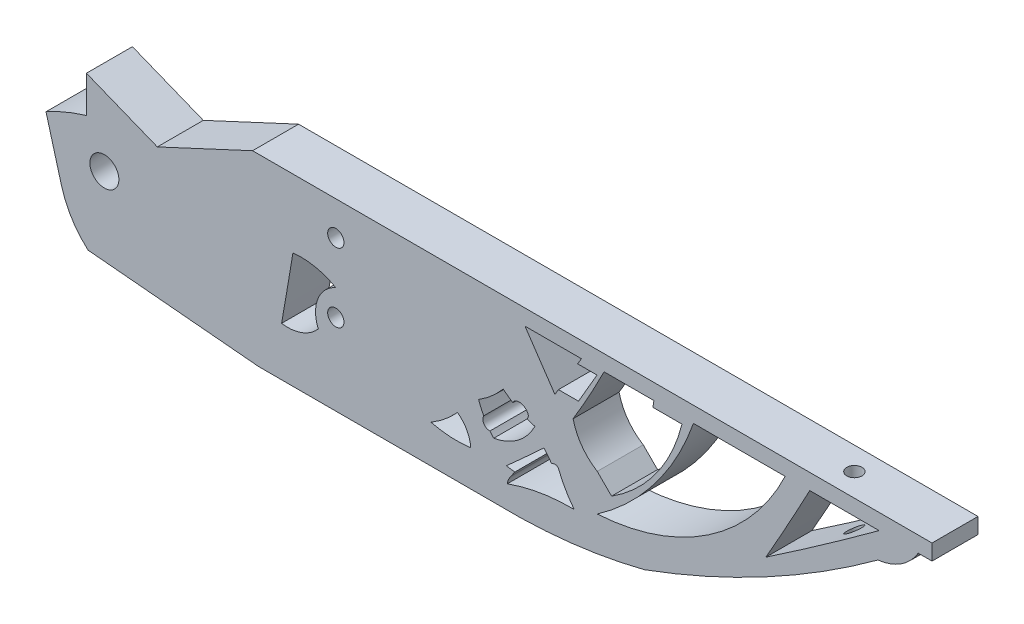
SolidWorks part; units mm, degrees
ref_plane "Front Plane" through (0, 0, 0) normal (0, 0, 1) x (1, 0, 0)
ref_plane "Top Plane" through (0, 0, 0) normal (0, 1, 0) x (1, 0, 0)
ref_plane "Right Plane" through (0, 0, 0) normal (1, 0, 0) x (0, 0, -1)
sketch "Sketch1" plane through (0, 0, 0) normal (0, 0, 1) x (1, 0, 0)
  line L1 (120.65, 25.4) -> (-120.65, 25.4)
  line L2 (120.65, 25.4) -> (120.65, -25.4)
  line L3 (120.65, -25.4) -> (-120.65, -25.4)
  line L4 (-120.65, 25.4) -> (-120.65, -25.4)
  line L5 (120.65, 25.4) -> (-120.65, -25.4) construction
  line L6 (120.65, -25.4) -> (-120.65, 25.4) construction
  point P0 (0, 0)
  dimension "D1" = 241.3
  dimension "D2" = 50.8
extrude "Boss-Extrude1" add sketch "Sketch1" along normal blind 12.7
sketch "Sketch3" plane through (0, 0, 12.7) normal (0, 0, 1) x (1, 0, 0)
  line L0 (0, 0) -> (-120.65, 0) construction
  line L1 (-120.65, 25.4) -> (-120.65, -25.4) construction
  circle A0 centre (-107.95, 0) radius 4
  dimension "D2" = 8
  dimension "D1" = 12.7
extrude "Cut-Extrude1" cut sketch "Sketch3" against normal through all
sketch "Sketch5" plane through (0, 0, 12.7) normal (0, 0, 1) x (1, 0, 0)
  line L0 (-120.65, -25.4) -> (120.65, -25.4) construction
  line L1 (-111.232, -5.4361) -> (-109.6883, -6.1074)
  line L2 (-107.95, 6.35) -> (-67.0151, 25.4)
  line L3 (120.65, 25.4) -> (-120.65, 25.4) construction
  line L4 (-67.0151, 25.4) -> (-120.65, 25.4)
  line L5 (-120.65, 25.4) -> (-120.65, -25.4)
  line L6 (-120.65, -25.4) -> (-65.3282, -25.4)
  line L7 (120.65, 13.8537) -> (120.65, -25.4)
  line L8 (120.65, -25.4) -> (0, -25.4)
  line L9 (120.65, 13.8537) -> (105.7036, 13.8537)
  line L13 (-112.4482, 4.482) -> (-117.3177, 9.3339)
  line L14 (-112.4482, -21.1143) -> (-65.3282, -25.4)
  arc A0 (0, -25.4) -> (105.7036, 13.8537) centre (3.5611, 126.9584) ccw
  arc A1 (-109.9582, -6.0241) -> (-114.0227, -1.8561) centre (-107.95, 0) ccw construction
  arc A2 (-107.95, 6.35) -> (-112.4482, 4.482) centre (-107.95, 0) ccw
  arc A5 (-117.3177, 9.3339) -> (-112.4482, -21.1143) centre (-96.4004, -2.9344) ccw
  point P15 (-116.1445, -2.9908)
  line M3 (-120.65, 25.4) -> (-120.65, -25.4)
  line M4 (-120.65, -25.4) -> (120.65, -25.4)
  line M5 (120.65, -25.4) -> (120.65, 25.4)
  line M6 (120.65, 25.4) -> (-120.65, 25.4)
  dimension "D1" = 152.4
  dimension "D2" = 12.7
  dimension "D3" = 45.1505
  dimension "D4" = 45.9039
extrude "Cut-Extrude2" cut sketch "Sketch5" against normal through all contours A2 L2 L1 M6 M3 M4 | A0 L8 M5 | A5 L5 L14 M4 region at (-102.0317, 17.7416, 12.7) region at (-105.9894, -22.0132, 12.7) region at (91.2141, -11.3337, 12.7)
sketch "Sketch6" plane through (0, 0, 12.7) normal (0, 0, 1) x (1, 0, 0)
  line L0 (-107.95, 0) -> (87.8661, 0) construction
  arc A0 (7.1222, -25.4) -> (105.7036, 13.8537) centre (3.5611, 126.9584) ccw construction
  circle A1 centre (19.05, 0) radius 3.1347
  dimension "D1" = 127
sketch "Sketch7" plane through (0, 0, 0) normal (0, 0, -1) x (-1, 0, 0)
  line L0 (44.0204, -2.9977) -> (44.0204, 16.0523) construction
  point P3 (44.0204, -2.9977)
  point P4 (44.0204, 16.0523)
  dimension "D1" = 19.05
sketch "Sketch8" plane through (0, 0, 0) normal (0, 0, -1) x (-1, 0, 0)
  point P0 (44.0204, 16.0523)
  point P3 (44.0204, -2.9977)
hole_wizard "#8 Clearance Hole1" positions "Sketch8" profile "Sketch9" hole size "#8" standard "ANSI Inch" end condition through all
sketch "Sketch9" plane through (-44.0204, 16.0523, 0) normal (1, 0, 0) x (0, 1, 0)
  line L0 (0, 0) -> (0, 12.7)
  line L1 (0, 12.7) -> (2.2479, 12.7)
  line L2 (2.2479, 12.7) -> (2.2479, 0)
  line L5 (2.2479, 0) -> (0, 0)
  line L11 (0, -6.35) -> (0, 107.95) construction
  dimension "Thru Hole Dia." = 4.4958
  dimension "Thru Hole Depth" = 12.7
ref_plane "Plane1" through (-114.3, 0, 0) normal (-1, 0, 0) x (0, 0, 1)
sketch "Sketch10" plane through (-114.3, 0, 0) normal (-1, 0, 0) x (0, 0, 1)
  line L0 (0, 0) -> (12.7, 0) construction
  line L1 (12.7, -3.1347) -> (12.7, 3.1347) construction
  circle A0 centre (6.0894, 0) radius 1.905
  dimension "D1" = 3.81
sketch "Sketch11" plane through (0, 0, 12.7) normal (0, 0, 1) x (1, 0, 0)
  line L0 (-93.8249, 12.9234) -> (-109.4459, 12.9234) construction
  line L1 (-107.95, 6.35) -> (-67.0151, 25.4) construction
  line L2 (-109.4459, 12.9234) -> (-109.4459, 11.5568) construction
  line L3 (-93.8249, 12.9234) -> (-109.4459, 5.6538)
  line L10 (-119.777, -9.3826) -> (-115.4906, -1.5141)
  line L11 (-115.4906, -1.5141) -> (-109.4459, 5.6538)
  line L12 (-124.0726, 6.1903) -> (-119.777, -9.3826)
  arc A0 (-117.3177, 9.3339) -> (-112.4482, -21.1143) centre (-96.4004, -2.9344) ccw construction
  circle A1 centre (-107.95, 0) radius 4 construction
  arc A4 (-124.0726, 6.1903) -> (-93.8249, 12.9234) centre (-97.649, -41.2057) cw
  dimension "D2" = 5.6538
extrude "Boss-Extrude2" add sketch "Sketch11" against normal up to surface (12.7 mm away) up to face at (-46.2683, 16.0523, 0)
sketch "Sketch18" plane through (0, 25.4, 0) normal (0, 1, 0) x (1, 0, 0)
  circle A0 centre (92.8548, -6.35) radius 2.0828
extrude "Cut-Extrude9" cut sketch "Sketch18" against normal through all contours A0
sketch "Sketch19" plane through (0, 0, 12.7) normal (0, 0, 1) x (1, 0, 0)
  line L3 (86.8867, 21.0579) -> (106.0483, 21.0579)
  line L4 (54.7502, 21.0579) -> (80.0838, 21.0579)
  line L5 (43.8283, 21.0579) -> (30.0654, 21.0579)
  line L6 (21.5195, 21.0579) -> (8.2267, 21.0579)
  line L7 (8.2267, 21.0579) -> (16.4852, 8.8568)
  line L8 (16.4852, 8.8568) -> (23.8201, 21.0579)
  line L9 (23.8201, 21.0579) -> (21.5195, 21.0579)
  arc A0 (106.0483, 21.0579) -> (74.7548, -0.9382) centre (-476.4178, 816.4626) cw
  arc A1 (86.8867, 21.0579) -> (74.7548, -0.9382) centre (-617.5859, 395.2635) cw
  arc A2 (80.0838, 21.0579) -> (28.1833, -13.9058) centre (24.5582, 47.4779) cw
  arc A3 (28.1833, -13.9058) -> (54.7502, 21.0579) centre (-12.7332, 44.7595) ccw
  arc A4 (30.0654, 21.0579) -> (21.5195, 5.5624) centre (-173.1779, 123.0437) cw
  arc A5 (43.8283, 21.0579) -> (28.1833, -3.6987) centre (9.3178, 25.5453) cw
  arc A6 (28.1833, -3.6987) -> (21.5195, 5.5624) centre (35.8652, 8.8568) cw
  arc A7 (3.09, -14.9046) -> (13.4624, -5.4583) centre (-508.9074, 557.7064) ccw
  arc A8 (13.4624, -5.4583) -> (18.8338, -14.9046) centre (-5.5007, -22.4915) cw
  arc A9 (18.8338, -14.9046) -> (3.09, -14.9046) centre (10.9619, 32.5583) cw
  arc A10 (2.2235, 3.0165) -> (-4.5776, -2.8864) centre (-19.0872, 20.7005) cw
  arc A11 (2.2235, 3.0165) -> (10.9619, -1.539) centre (16.8059, 20.3296) ccw
  arc A12 (10.9619, -1.539) -> (-0.4071, -10.0726) centre (-3.0644, 5.3078) cw
  arc A13 (-4.5776, -2.8864) -> (-0.4071, -10.0726) centre (15.1613, 3.7659) ccw
  arc A14 (-10.4164, -8.9177) -> (-6.7592, -15.5263) centre (-15.593, -16.0987) cw
  arc A15 (-6.7592, -15.5263) -> (-17.7308, -14.9046) centre (-10.6309, 13.2663) cw
  arc A16 (-17.7308, -14.9046) -> (-10.4164, -8.9177) centre (-33.6495, 12.0056) ccw
extrude "Cut-Extrude10" cut sketch "Sketch19" against normal through all
pattern_linear "LPattern1" [suppressed] count 5 spacing 6.35 of bodies 117
sketch "Sketch20" plane through (0, 0, 12.7) normal (0, 0, 1) x (1, 0, 0)
  line L0 (-112.9039, 9.7778) -> (-112.9039, 20.995)
  line L2 (-112.9039, 20.995) -> (-92.9368, 13.0011)
  line L3 (-92.9368, 13.0011) -> (-112.9039, 9.7778)
extrude "Boss-Extrude3" add sketch "Sketch20" against normal up to vertex (12.7 mm away) up to point (-124.0726, 6.1903, 0)
sketch "Sketch22" plane through (0, 0, 0) normal (0, 0, -1) x (-1, 0, 0)
  line L0 (-120.65, 21.0579) -> (-116.84, 21.0579)
  line L1 (-120.65, 13.8537) -> (-120.65, 25.4) construction
  line L10 (-120.65, 21.0579) -> (-120.65, 13.8537)
  line L11 (-120.65, 13.8537) -> (-105.7036, 13.8537)
  arc A0 (-116.84, 21.0579) -> (-105.7036, 13.8537) centre (-104.0685, 28.5907) ccw
  dimension "D18" = 14.8275
  dimension "D1" = 3.81
extrude "Cut-Extrude12" cut sketch "Sketch22" against normal through all
sketch "Sketch23" plane through (0, 0, 0) normal (0, 0, -1) x (-1, 0, 0)
  line L2 (-120.65, 21.0579) -> (-120.65, 25.4) construction
  arc A5 (-105.7036, 13.8537) -> (-7.1222, -25.4) centre (-3.5611, 126.9584) ccw
  arc A6 (-105.7036, 13.8537) -> (-41.2201, -20.7154) centre (49.027, 225.0536) ccw
  arc M3 (-105.7036, 13.8537) -> (-7.1222, -25.4) centre (-3.5611, 126.9584) ccw
  dimension "D1" = 152.4
  dimension "D2" = 261.8148
  dimension "D3" = 79.4299
extrude "Cut-Extrude13" cut sketch "Sketch23" against normal through all contours A6 M3 region at (74.7893, -5.9071, 0)
sketch "Sketch24" plane through (0, 0, 0) normal (0, 0, -1) x (-1, 0, 0)
  line L0 (44.0204, -2.9977) -> (44.0204, 16.0523) construction
  line L1 (-80.0838, 21.0579) -> (-54.7502, 21.0579) construction
  arc A0 (44.0204, 4.1309) -> (55.876, 6.5273) centre (53.6319, -12.8946) cw
  arc A1 (55.876, 6.5273) -> (59.0043, -11.8919) centre (1722.1416, 280.0452) ccw
  arc A2 (59.0043, -11.8919) -> (48.8565, -8.1533) centre (57.3207, -0.8203) cw
  arc A3 (48.8565, -8.1533) -> (44.0204, 4.1309) centre (40.2964, -4.4292) ccw
  dimension "D1" = 19.5512
  dimension "D2" = 1688.5654
  dimension "D3" = 11.1989
  dimension "D4" = 9.3351
  dimension "D5" = 22.5656
  dimension "D6" = 31.1257
  dimension "D7" = 35.901
  dimension "D8" = 38.1452
  dimension "D9" = 39.5899
  dimension "D10" = 41.2735
  dimension "D11" = 258.9872
extrude "Cut-Extrude14" cut sketch "Sketch24" against normal through all
sketch "Sketch25" plane through (0, 0, 0) normal (0, 0, -1) x (-1, 0, 0)
  line L2 (-16.1464, -7.9047) -> (-15.512, -8.0981)
  line L3 (-4.3499, -16.7759) -> (-5.4267, -15.2335)
  line L4 (-5.4267, -15.2335) -> (-15.512, -8.0981)
  line L6 (-80.0838, 21.0579) -> (-54.7502, 21.0579) construction
  arc A0 (-4.3499, -16.7759) -> (-3.3328, -19.1048) centre (-8.2887, -19.8825) cw
  arc A1 (-16.1464, -7.9047) -> (-17.4118, -8.2208) centre (-16.5158, -9.1168) ccw
  arc A3 (-17.4118, -8.2208) -> (-21.8096, -15.9981) centre (-45.3139, 2.4248) cw
  arc A4 (-21.8096, -15.9981) -> (-3.3328, -19.1048) centre (-21.1264, -68.4326) cw
  arc A5 (-18.8338, -14.9046) -> (-3.09, -14.9046) centre (-10.9619, 32.5583) ccw construction
  dimension "D1" = 5.0165
  dimension "D2" = 1.2671
  dimension "D3" = 29.864
  dimension "D4" = 52.439
  dimension "D5" = 60.7344
  dimension "D6" = 84.2387
  dimension "D7" = 84.9219
  dimension "D8" = 88.6365
  dimension "D9" = 89.5325
  dimension "D10" = 97.7596
  dimension "D11" = 89.9019
  dimension "D12" = 101.6984
  dimension "D13" = 102.7155
  dimension "D14" = 90.5363
  dimension "D15" = 100.6216
  dimension "D16" = 18.6331
extrude "Cut-Extrude15" cut sketch "Sketch25" against normal through all
sketch "Sketch26" plane through (0, 0, 0) normal (0, 0, -1) x (-1, 0, 0)
  line L0 (-8.8542, -0.8638) -> (-9.1783, 0)
  line L1 (107.95, 0) -> (-87.8661, 0) construction
  line L2 (-4.8856, 1.0865) -> (-5.2499, 1.6746)
  arc A0 (-10.9619, -1.539) -> (-2.2235, 3.0165) centre (-16.8059, 20.3296) ccw construction
  arc A1 (-9.1783, 0) -> (-5.2499, 1.6746) centre (-6.6651, -0.4506) cw
  arc A2 (1.4272, -8.8317) -> (3.1791, -6.1088) centre (1.5839, -7.0075) ccw
  arc A3 (0.4071, -10.0726) -> (4.5776, -2.8864) centre (-15.1613, 3.7659) ccw construction
  arc A4 (-8.8542, -0.8638) -> (-4.8856, 1.0865) centre (-12.5523, 11.6742) ccw
  arc A5 (1.4272, -8.8317) -> (3.1791, -6.1088) centre (5.4965, -9.5248) cw
  dimension "D1" = 2.5533
  dimension "D2" = 1.8309
  dimension "D10" = 13.0721
  dimension "D11" = 4.1278
  dimension "D3" = 55.8252
  dimension "D4" = 57.4204
  dimension "D5" = 63.8899
  dimension "D6" = 64.2542
  dimension "D7" = 65.6694
  dimension "D8" = 67.8586
  dimension "D9" = 68.1827
extrude "Cut-Extrude16" cut sketch "Sketch26" against normal through all
sketch "Sketch27" plane through (0, 0, 0) normal (0, 0, -1) x (-1, 0, 0)
  line L0 (-43.5541, 19.3012) -> (-51.5785, 19.3012)
  line L1 (-28.1833, -3.6987) -> (-32.1378, -7.6533)
  line L2 (-43.5541, 19.3012) -> (-43.0572, 19.3012)
  arc A0 (-43.8283, 21.0579) -> (-28.1833, -3.6987) centre (-9.3178, 25.5453) ccw construction
  arc A1 (-51.5785, 19.3012) -> (-32.1378, -7.6533) centre (-8.3802, 29.9697) ccw
  arc A3 (-43.0572, 19.3012) -> (-28.1833, -3.6987) centre (-4.4439, 27.9629) ccw
  dimension "D1" = 44.4962
  dimension "D2" = 39.5729
  dimension "D3" = 54.4698
  dimension "D4" = 62.4942
  dimension "D5" = 62.9911
  dimension "D6" = 73.9105
  dimension "D7" = 97.6681
extrude "Cut-Extrude17" cut sketch "Sketch27" against normal through all
sketch "Sketch28" plane through (0, 0, 0) normal (0, 0, -1) x (-1, 0, 0)
  line L0 (-22.7681, 19.308) -> (-28.1274, 19.308)
  line L1 (-16.4852, 8.8568) -> (-23.8201, 21.0579) construction
  line L2 (-17.4699, 10.4947) -> (-23.0003, 10.4947)
  line L3 (-23.0003, 10.4947) -> (-28.1274, 19.308)
  line L4 (-22.7681, 19.308) -> (-17.4699, 10.4947)
  dimension "D1" = 76.4742
  dimension "D2" = 81.7724
  dimension "D3" = 82.0046
  dimension "D4" = 87.1317
extrude "Cut-Extrude18" cut sketch "Sketch28" against normal through all
